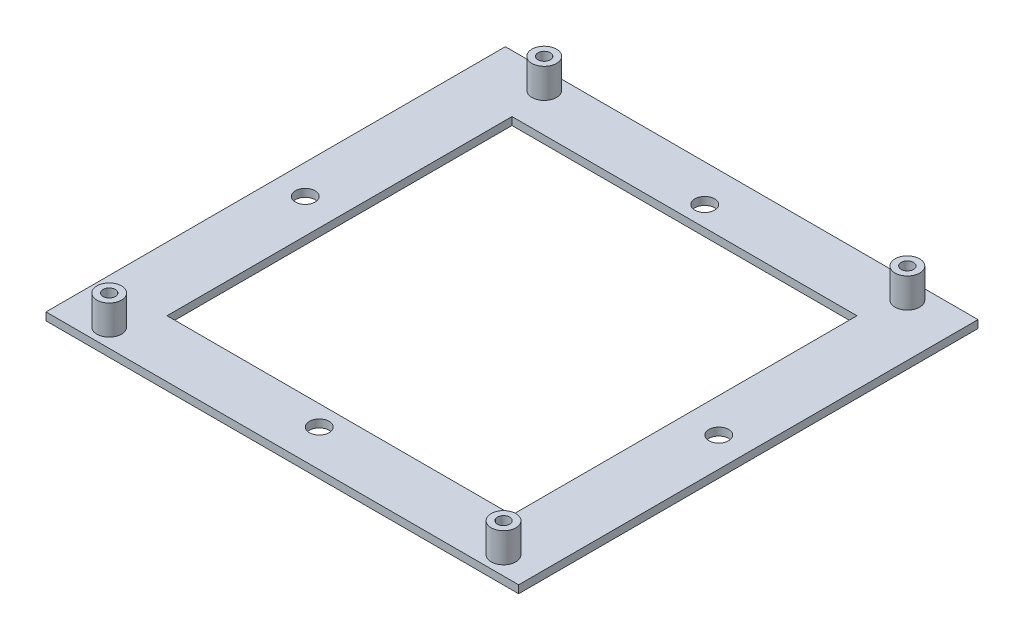
SolidWorks part; units mm, degrees
ref_plane "Front Plane" through (0, 0, 0) normal (0, 0, 1) x (1, 0, 0)
ref_plane "Top Plane" through (0, 0, 0) normal (0, 1, 0) x (1, 0, 0)
ref_plane "Right Plane" through (0, 0, 0) normal (1, 0, 0) x (0, 0, -1)
sketch "Sketch1" plane through (0, 0, 0) normal (0, 1, 0) x (1, 0, 0)
  line L1 (-47.95, -46.6) -> (47.95, -46.6)
  line L2 (-47.95, -46.6) -> (-47.95, 46.6)
  line L3 (-47.95, 46.6) -> (47.95, 46.6)
  line L4 (47.95, -46.6) -> (47.95, 46.6)
  line L5 (-47.95, -46.6) -> (47.95, 46.6) construction
  line L6 (-47.95, 46.6) -> (47.95, -46.6) construction
  line L7 (-35, -35) -> (35, -35)
  line L8 (-35, -35) -> (-35, 35)
  line L9 (-35, 35) -> (35, 35)
  line L10 (35, -35) -> (35, 35)
  line L11 (-35, -35) -> (35, 35) construction
  line L12 (-35, 35) -> (35, -35) construction
  circle A0 centre (0, 39.1) radius 2
  circle A1 centre (41.95, 0) radius 2
  circle A2 centre (0, -39.1) radius 2
  circle A3 centre (-41.95, 0) radius 2
  point P0 (0, 0)
  point P6 (0, 0)
  point P11 (0, 39.1)
  point P12 (0, -39.1)
  point P13 (41.95, 0)
  point P14 (-41.95, 0)
extrude "Boss-Extrude1" add sketch "Sketch1" along normal blind 1.58
sketch "Sketch2" plane through (0, 1.58, 0) normal (0, 1, 0) x (1, 0, 0)
  circle A0 centre (37.355, 42.8635) radius 2.5
  circle A1 centre (-36.325, 42.8625) radius 2.5
  circle A2 centre (-38.865, -42.8625) radius 2.5
  circle A3 centre (41.145, -42.8625) radius 2.5
  point P0 (37.355, 42.8635)
  point P5 (0, 0)
  point P6 (0, 0)
  point P7 (0, 0)
  point P8 (0, 0)
  point P9 (0, 0)
  point P12 (0, 0)
  point P15 (0, 0)
  point P16 (0, 0)
extrude "Boss-Extrude2" add sketch "Sketch2" along normal blind 6
hole_wizard "M3x0.5 Tapped Hole2" positions "3DSketch2" profile "Sketch4" tap size "M3x0.5" standard "ANSI Metric"
sketch3d "3DSketch2"
  line L0 (-36.325, 7.58, -42.8625) -> (-36.325, 1.58, -42.8625) construction
  line L1 (-38.865, 7.58, 42.8625) -> (-38.865, 1.58, 42.8625) construction
  line L2 (41.145, 7.58, 42.8625) -> (41.145, 1.58, 42.8625) construction
  line L3 (37.355, 7.58, -42.8635) -> (37.355, 1.58, -42.8635) construction
  point P0 (-36.325, 7.58, -42.8625)
  point P4 (-38.865, 7.58, 42.8625)
  point P8 (41.145, 7.58, 42.8625)
  point P12 (37.355, 7.58, -42.8635)
sketch "Sketch4" plane through (-36.325, 7.58, -42.8625) normal (1, 0, 0) x (0, 0, 1)
  line L0 (0, 0) -> (0, 6.7511)
  line L1 (0, 6.7511) -> (1.25, 6)
  line L2 (1.25, 6) -> (1.25, 0)
  line L5 (1.25, 0) -> (0, 0)
  line L10 (0, 6.7511) -> (-1.25, 6) construction
  line L11 (0, -6.35) -> (0, 107.95) construction
  dimension "Tap Drill Dia." = 2.5
  dimension "Tap Drill Depth" = 6
  dimension "Drill Angle" = 118
cosmetic thread "Hole Thread5" parameters "D1"=6, "D2"=3
cosmetic thread "Hole Thread6" parameters "D1"=6, "D2"=3
cosmetic thread "Hole Thread7" parameters "D1"=6, "D2"=3
cosmetic thread "Hole Thread8" parameters "D1"=6, "D2"=3
